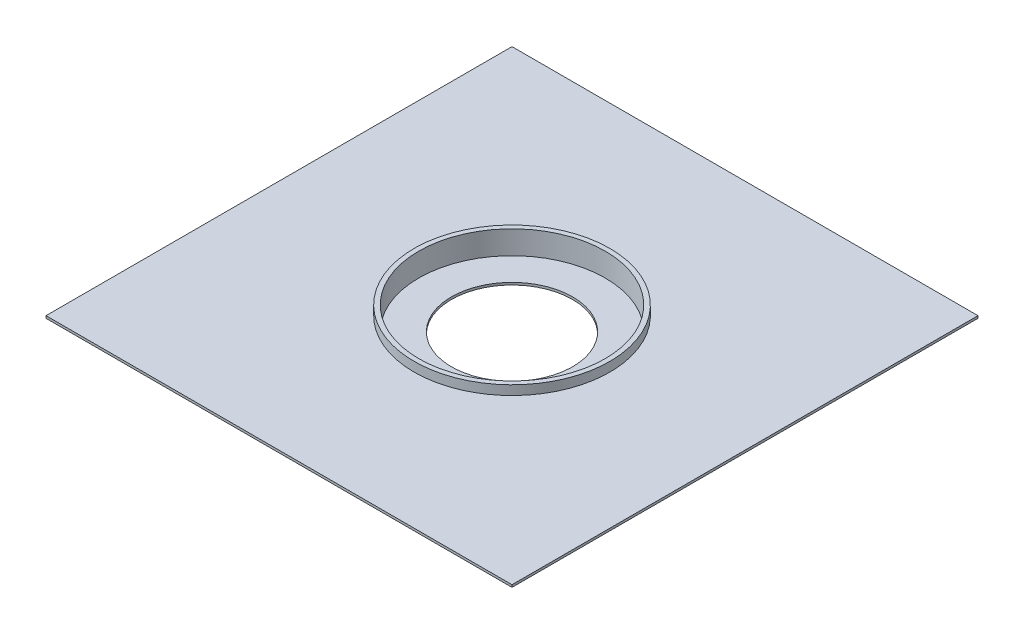
SolidWorks part; units mm, degrees
material "Plain Carbon Steel"
ref_plane "Front Plane" through (0, 0, 0) normal (0, 0, 1) x (1, 0, 0)
ref_plane "Top Plane" through (0, 0, 0) normal (0, 1, 0) x (1, 0, 0)
ref_plane "Right Plane" through (0, 0, 0) normal (1, 0, 0) x (0, 0, -1)
sketch "Sketch1" plane through (0, 0, 0) normal (0, 1, 0) x (1, 0, 0)
  line L1 (0, 0) -> (200, 0)
  line L2 (0, 0) -> (0, -200)
  line L3 (0, -200) -> (200, -200)
  line L4 (200, 0) -> (200, -200)
  dimension "D1" = 200
  dimension "D2" = 200
extrude "Boss-Extrude3" add sketch "Sketch1" along normal blind 1
sketch "Sketch10" plane through (0, 1, 0) normal (0, 1, 0) x (1, 0, 0)
  circle A0 centre (100, -100) radius 40
extrude "Cut-Extrude2" cut sketch "Sketch10" against normal blind 1
sketch "Sketch13" plane through (0, 0, 0) normal (0, -1, 0) x (1, 0, 0)
  circle A0 centre (100, 100) radius 40
  circle A1 centre (100, 100) radius 42
  dimension "D1" = 2
extrude "Boss-Extrude6" add sketch "Sketch13" along normal blind 5 and the other way blind 5
sketch "Sketch14" plane through (0, -5, 0) normal (0, -1, 0) x (1, 0, 0)
  circle A0 centre (100, 100) radius 26
  circle A1 centre (100, 100) radius 42
extrude "Boss-Extrude7" add sketch "Sketch14" along normal blind 1
